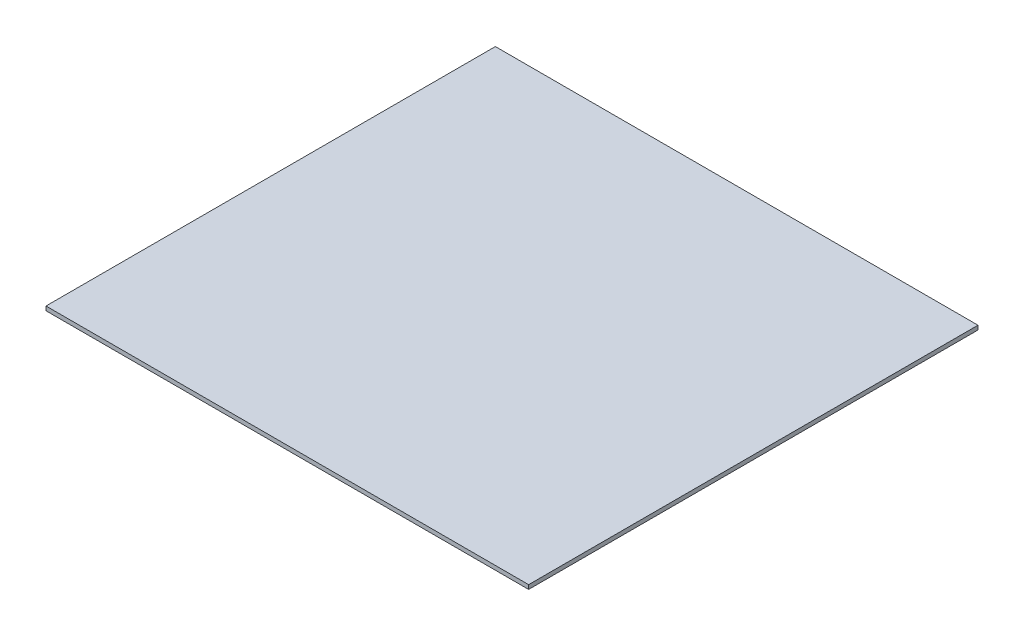
SolidWorks part; units mm, degrees
material "Acrylic (Medium-high impact)"
ref_plane "Front Plane" through (0, 0, 0) normal (0, 0, 1) x (1, 0, 0)
ref_plane "Top Plane" through (0, 0, 0) normal (0, 1, 0) x (1, 0, 0)
ref_plane "Right Plane" through (0, 0, 0) normal (1, 0, 0) x (0, 0, -1)
sketch "Sketch1" plane through (0, 0, 0) normal (0, 1, 0) x (1, 0, 0)
  line L1 (-184.15, -171.45) -> (184.15, -171.45)
  line L2 (-184.15, -171.45) -> (-184.15, 171.45)
  line L3 (-184.15, 171.45) -> (184.15, 171.45)
  line L4 (184.15, -171.45) -> (184.15, 171.45)
  line L5 (-184.15, -171.45) -> (184.15, 171.45) construction
  line L6 (-184.15, 171.45) -> (184.15, -171.45) construction
  point P0 (0, 0)
  dimension "D1" = 342.9
  dimension "D2" = 368.3
extrude "Boss-Extrude1" add sketch "Sketch1" along normal blind 3.175
